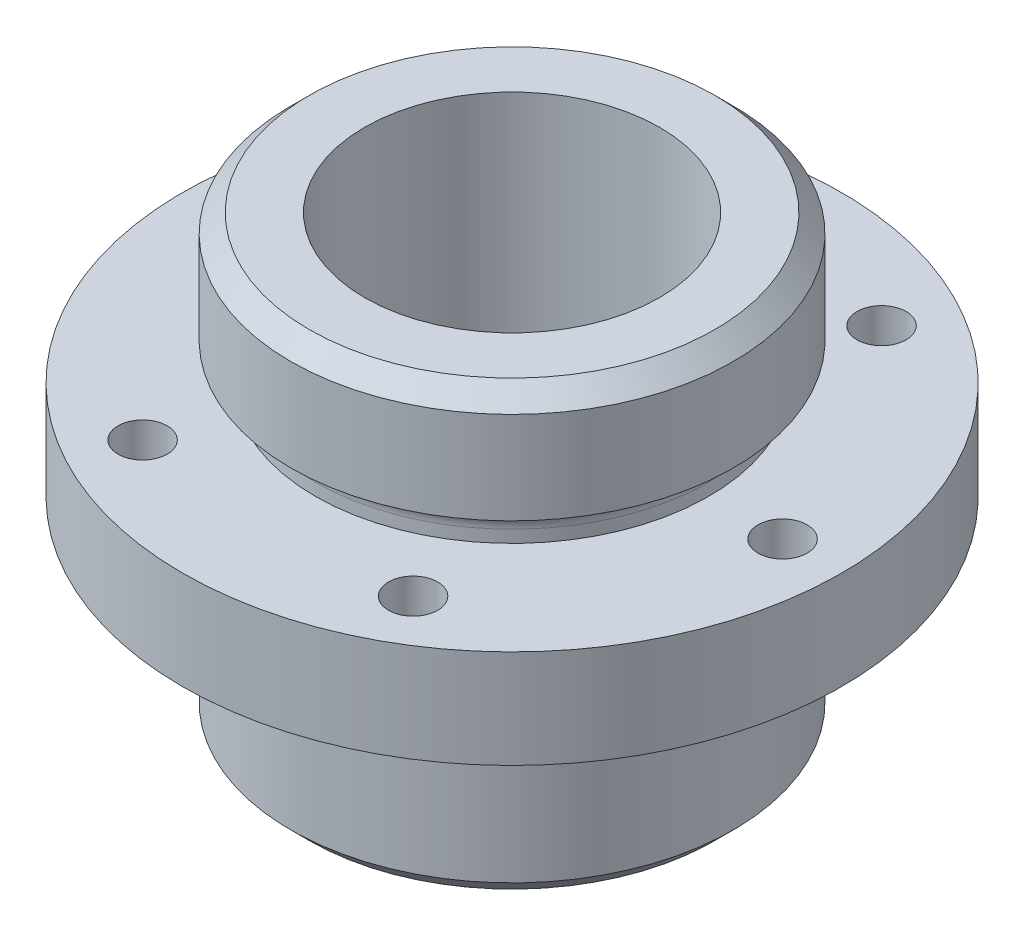
SolidWorks part; units mm, degrees
ref_plane "Front Plane" through (0, 0, 0) normal (0, 0, 1) x (1, 0, 0)
ref_plane "Top Plane" through (0, 0, 0) normal (0, 1, 0) x (1, 0, 0)
ref_plane "Right Plane" through (0, 0, 0) normal (1, 0, 0) x (0, 0, -1)
sketch "Sketch1" plane through (0, 0, 0) normal (0, 1, 0) x (1, 0, 0)
  line L0 (-53.6144, 0) -> (53.6144, 0) construction
  circle A0 centre (0, 0) radius 53.6144
  circle A1 centre (-44, 0) radius 4
  circle A2 centre (-22, 38.1051) radius 4
  circle A3 centre (22, 38.1051) radius 4
  circle A4 centre (44, 0) radius 4
  circle A5 centre (22, -38.1051) radius 4
  circle A6 centre (-22, -38.1051) radius 4
  point P19 (0, 0)
  dimension "D1" = 8
  dimension "D3" = 44
  dimension "D2" = 6
extrude "Boss-Extrude1" add sketch "Sketch1" along normal blind 16
sketch "Sketch3" plane through (0, 16, 0) normal (0, 1, 0) x (1, 0, 0)
  circle A0 centre (0, 0) radius 32
extrude "Boss-Extrude2" add sketch "Sketch3" along normal blind 6
sketch "Sketch4" plane through (0, 22, 0) normal (0, 1, 0) x (1, 0, 0)
  circle A0 centre (0, 0) radius 36
extrude "Boss-Extrude3" add sketch "Sketch4" along normal blind 18
sketch "Sketch5" plane through (0, 0, 0) normal (0, -1, 0) x (1, 0, 0)
  circle A0 centre (0, 0) radius 32
extrude "Boss-Extrude4" add sketch "Sketch5" along normal blind 8
sketch "Sketch6" plane through (0, -8, 0) normal (0, -1, 0) x (1, 0, 0)
  circle A0 centre (0, 0) radius 36
extrude "Boss-Extrude5" add sketch "Sketch6" along normal blind 24
fillet "Fillet2" radius 4 2 edges at (0, -8, -32) (0, 22, 32)
chamfer "Chamfer2" distance 3 angle 45 2 edges at (0, -32, -36) (0, 40, 36)
sketch "Sketch7" plane through (0, 40, 0) normal (0, 1, 0) x (1, 0, 0)
  circle A0 centre (0, 0) radius 24
extrude "Cut-Extrude1" cut sketch "Sketch7" against normal up to surface (72 mm away) up to face at (0, -32, -33)
